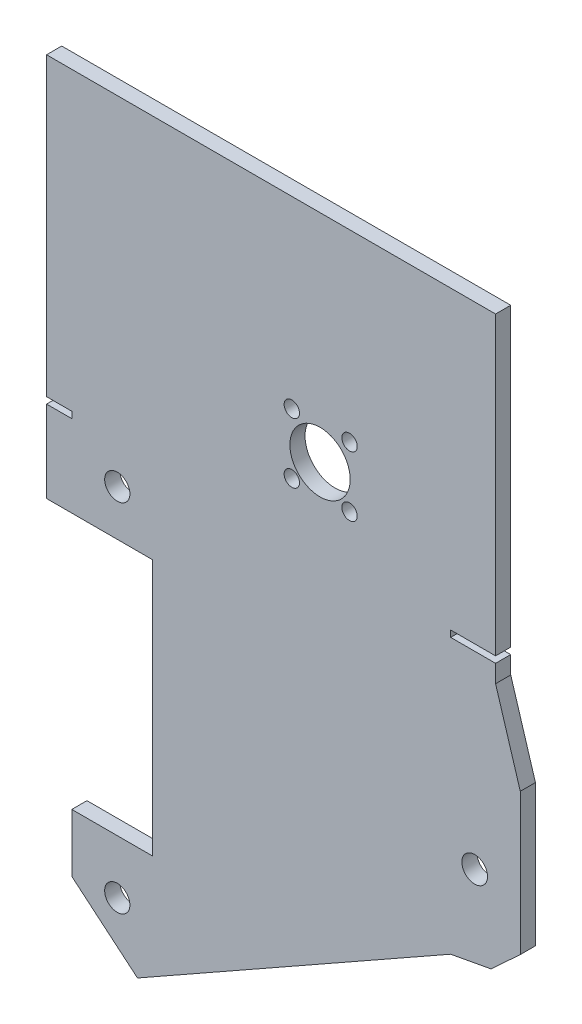
SolidWorks part; units mm, degrees
ref_plane "Front Plane" through (0, 0, 0) normal (0, 0, 1) x (1, 0, 0)
ref_plane "Top Plane" through (0, 0, 0) normal (0, 1, 0) x (1, 0, 0)
ref_plane "Right Plane" through (0, 0, 0) normal (1, 0, 0) x (0, 0, -1)
sketch "Sketch1" plane through (0, 0, 0) normal (0, 0, 1) x (1, 0, 0)
  line L0 (0, 0) -> (88.9, 0)
  line L1 (88.9, 0) -> (88.9, -3.5)
  line L2 (88.9, -3.5) -> (93.7917, -19.5)
  line L3 (93.7917, -19.5) -> (93.7917, -47.5)
  line L4 (0, 0) -> (0, -16.2)
  line L5 (0, -16.2) -> (21, -16.2)
  line L6 (21, -16.2) -> (21, -67)
  line L7 (21, -67) -> (5, -67)
  line L8 (5, -67) -> (5, -78.5)
  line L9 (5, -78.5) -> (18, -89.4083)
  line L10 (18, -89.4083) -> (80, -54.3304)
  line L11 (80, -54.3304) -> (88, -52.8477)
  line L12 (88, -52.8477) -> (93.7917, -47.5)
  dimension "D1" = 88.9
  dimension "D2" = 3.5
  dimension "D3" = 163
  dimension "D4" = 16
  dimension "D5" = 28
  dimension "D6" = 89.4083
  dimension "D7" = 21
  dimension "D8" = 50.8
  dimension "D9" = 16
  dimension "D10" = 11.5
  dimension "D11" = 130
  dimension "D12" = 13
  dimension "D13" = 110.5
  dimension "D14" = 62
  dimension "D15" = 8
  dimension "D16" = 161
extrude "Boss-Extrude1" add sketch "Sketch1" along normal blind 3
sketch "Sketch2" plane through (0, 0, 0) normal (0, 1, 0) x (1, 0, 0)
  line L0 (45.8978, 14) -> (40.3978, 14) construction
  line L1 (0, -3) -> (88.9, -3)
  line L2 (0, -3) -> (0, 54)
  line L3 (0, 54) -> (88.9, 54)
  line L4 (88.9, -3) -> (88.9, 54)
  circle A0 centre (40.3978, 8.5) radius 1.5
  circle A1 centre (40.3978, 20) radius 1.5
  circle A2 centre (51.8978, 8.5) radius 1.5
  circle A3 centre (51.8978, 20) radius 1.5
  ellipse E0 centre (45.8978, 14) end of major axis (45.8978, 8) minor radius 5.5
  dimension "D9" = 3
  dimension "D10" = 3
  dimension "D11" = 3
  dimension "D12" = 3
  dimension "D1" = 88.9
  dimension "D2" = 57
  dimension "D3" = 45.8978
  dimension "D4" = 5.5
  dimension "D5" = 11.5
  dimension "D6" = 23
  dimension "D7" = 11.5
  dimension "D8" = 17
  dimension "D13" = 12
  dimension "D14" = 11
extrude "Boss-Extrude2" add sketch "Sketch2" along normal blind 3
ref_plane "Plane1" through (85.9, 0, 0) normal (1, 0, 0) x (0, 0, -1)
sketch "Sketch3" plane through (85.9, 0, 0) normal (1, 0, 0) x (0, 0, -1)
  line L0 (11.5, 0) -> (0, 0)
  line L1 (0, 0) -> (54, 0) construction
  line L2 (0, 0) -> (0, -11.5)
  line L3 (0, -19.5) -> (0, -3.5) construction
  line L4 (0, -11.5) -> (11.5, 0)
  dimension "D1" = 11.5
  dimension "D2" = 11.5
extrude "Boss-Extrude3" add sketch "Sketch3" against normal blind 84.5
sketch "Sketch4" plane through (0, 0, 0) normal (0, 0, -1) x (-1, 0, 0)
  line L0 (-1.4, -11.5) -> (-85.9, -11.5) construction
  line L1 (-81.4, -11.5) -> (-6.4, -11.5)
  line L2 (-81.4, -11.5) -> (-81.4, 0)
  line L3 (-81.4, 0) -> (-6.4, 0)
  line L4 (-6.4, -11.5) -> (-6.4, 0)
  line L5 (-50.8976, 0) -> (-85.9, 0) construction
  line L6 (-85.9, 13.7659) -> (-85.9, -13.7659) construction
  dimension "D1" = 75
  dimension "D2" = 4.5
extrude "Cut-Extrude2" cut sketch "Sketch4" along normal blind 84.5
sketch "Sketch6" plane through (0, 0, 3) normal (0, 0, 1) x (1, 0, 0)
  line L0 (0, 3) -> (0, -16.2) construction
  line L1 (0, 3) -> (88.9, 3) construction
  circle A0 centre (14, -77.66) radius 2.5
  circle A1 centre (84.763, -37.386) radius 2.54
  circle A2 centre (14, -7.16) radius 2.5
  dimension "D1" = 5
  dimension "D2" = 5
  dimension "D3" = 5.08
  dimension "D4" = 14
  dimension "D5" = 10.16
  dimension "D6" = 70.5
  dimension "D7" = 14
  dimension "D8" = 40.386
  dimension "D9" = 70.763
extrude "Cut-Extrude3" cut sketch "Sketch6" against normal blind 84.5
sketch "Sketch7" plane through (0, 0, 0) normal (0, -1, 0) x (1, 0, 0)
  line L1 (88.9, -54) -> (0, -54)
  line L2 (88.9, -54) -> (88.9, 0)
  line L3 (88.9, 0) -> (0, 0)
  line L4 (0, -54) -> (0, 0)
extrude "Cut-Extrude4" cut sketch "Sketch7" against normal through all both and the other way through all
sketch "Sketch8" plane through (0, 0, 0) normal (0, 0, -1) x (-1, 0, 0)
  line L0 (-88.9, 3) -> (0, 3) construction
  line L1 (-88.9, 3) -> (0, 3)
  line L2 (-88.9, 3) -> (-88.9, 59.896)
  line L3 (-88.9, 59.896) -> (0, 59.896)
  line L4 (0, 3) -> (0, 59.896)
  line L5 (-54.144, 17.1224) -> (-48.175, 17.1224) construction
  line L6 (-14, -77.66) -> (-84.763, -77.66) construction
  line L7 (-84.763, -77.66) -> (-84.763, -37.386) construction
  line L8 (-49.3815, -77.66) -> (-49.3815, 51.3441) construction
  line L9 (-58.3815, 3) -> (-58.3815, 17.1224) construction
  line L10 (-58.3815, 17.1224) -> (-54.144, 17.1224) construction
  circle A0 centre (-54.144, 17.1224) radius 5.969
  circle A1 centre (-48.556, 23.4724) radius 1.524
  circle A2 centre (-48.556, 11.5344) radius 1.524
  circle A3 centre (-59.986, 23.4724) radius 1.524
  circle A4 centre (-59.986, 11.5344) radius 1.524
  dimension "D8" = 11.938
  dimension "D9" = 3.048
  dimension "D10" = 3.048
  dimension "D11" = 3.048
  dimension "D12" = 3.048
  dimension "D1" = 56.896
  dimension "D2" = 88.9
  dimension "D3" = 14.1224
  dimension "D4" = 5.588
  dimension "D5" = 4.7625
  dimension "D6" = 11.938
  dimension "D7" = 5.588
  dimension "D14" = 11.43
extrude "Boss-Extrude4" add sketch "Sketch8" against normal up to surface (3 mm away) up to face at (16.5, -77.66, 3)
sketch "Sketch10" plane through (0, 0, 0) normal (0, 0, -1) x (-1, 0, 0)
  line L0 (-88.9, -3.5) -> (-88.9, 59.896) construction
  line L1 (0, 0) -> (-5.08, 0)
  line L2 (0, 0) -> (0, 1.27)
  line L3 (0, 1.27) -> (-5.08, 1.27)
  line L4 (-5.08, 0) -> (-5.08, 1.27)
  line L5 (-80.01, 0) -> (-88.9, 0)
  line L6 (-80.01, 0) -> (-80.01, 1.27)
  line L7 (-80.01, 1.27) -> (-88.9, 1.27)
  line L8 (-88.9, 0) -> (-88.9, 1.27)
  dimension "D1" = 5.08
  dimension "D2" = 1.27
  dimension "D3" = 8.89
  dimension "D4" = 1.27
extrude "Cut-Extrude5" cut sketch "Sketch10" against normal blind 10
